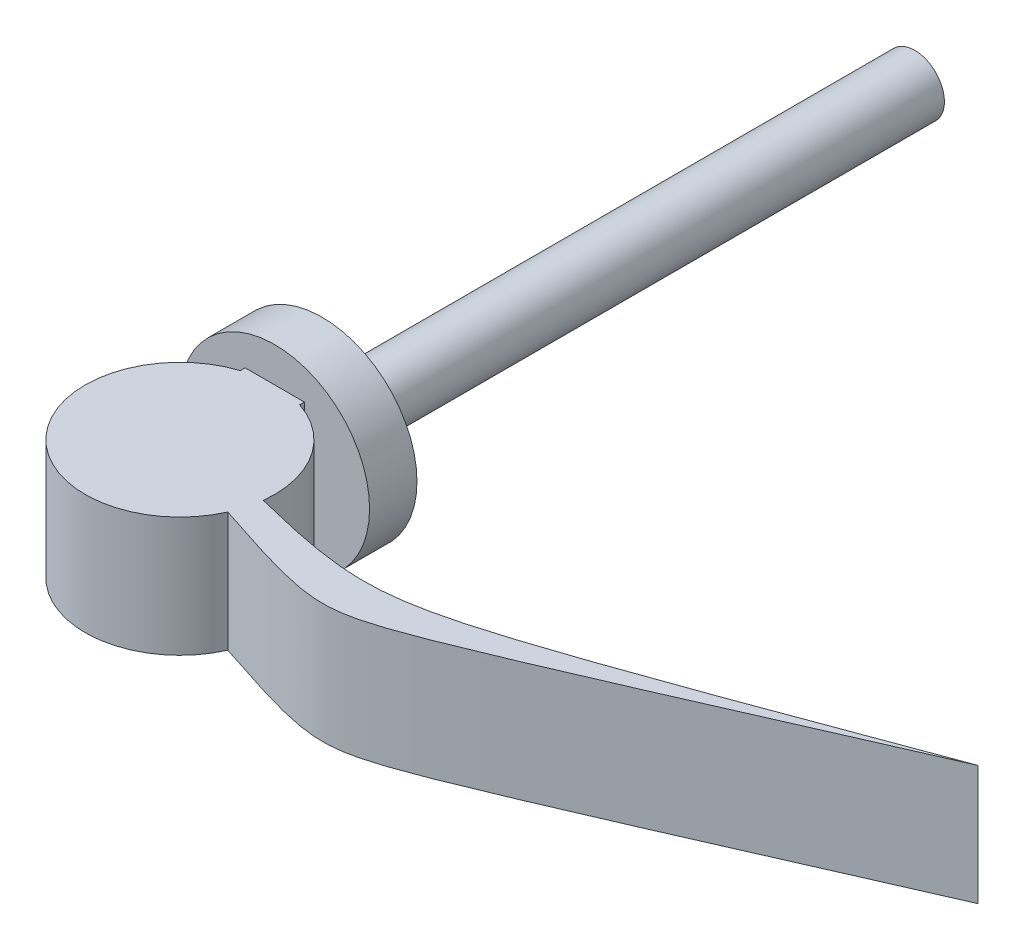
SolidWorks part; units mm, degrees
material "Zero density"
ref_plane "Piano frontale" through (0, 0, 0) normal (0, 0, 1) x (1, 0, 0)
ref_plane "Piano superiore" through (0, 0, 0) normal (0, 1, 0) x (1, 0, 0)
ref_plane "Piano destro" through (0, 0, 0) normal (1, 0, 0) x (0, 0, -1)
sketch "Schizzo1" plane through (0, 0, 0) normal (0, 0, 1) x (1, 0, 0)
  circle A0 centre (0, 0) radius 2.5
  dimension "D1" = 5
extrude "GamboVite" add sketch "Schizzo1" along normal blind 50
sketch "Schizzo2" plane through (0, 0, 50) normal (0, 0, 1) x (1, 0, 0)
  circle A0 centre (0, 0) radius 8
  dimension "D1" = 16
extrude "Piattello" add sketch "Schizzo2" along normal blind 4
sketch "Schizzo3" plane through (0, 0, 0) normal (0, 1, 0) x (1, 0, 0)
  line L0 (-8, -54) -> (8, -54) construction
  line L1 (-2.5, -54) -> (2.5, -54)
  line L2 (-2.5, -54) -> (-2.5, -56)
  line L4 (2.5, -54) -> (2.5, -56)
  line L6 (0, -8.8) -> (0, 8.8) construction
  line L7 (2.5, 0) -> (-2.5, 0) construction
  arc A0 (-2.5, -56) -> (2.5, -56) centre (0, -62) ccw
  point P10 (0, -54)
  dimension "D1" = 13
  dimension "D2" = 2
extrude "AggancioLevetta" add sketch "Schizzo3" along normal blind 5.05 and the other way blind 5.05
sketch "Schizzo4" plane through (0, 5.05, 0) normal (0, 1, 0) x (1, 0, 0)
  line L1 (-8, -54) -> (8, -54) construction
  arc A0 (7.9473, -62.9166) -> (7.3032, -65.2656) centre (0, -62) ccw
  conic Q0 (7.3032, -65.2656) -> (57.4656, -52.1326) control (18.8516, -69.1322) rho 0.846412
  conic Q1 (7.9473, -62.9166) -> (57.4656, -52.1326) control (20.1849, -66.0318) rho 0.759
  dimension "D1" = 16
  dimension "D2" = 49.5183
  dimension "D3" = 8.9166
  dimension "D4" = 11.2656
  dimension "D6" = 10.7841
  dimension "D7" = 12.2376
  dimension "D9" = 3.1152
  dimension "D10" = 13.627
  dimension "D11" = 2.2642
extrude "LevaParteSinistra" add sketch "Schizzo4" against normal up to surface (10.1 mm away) up to face at (0, -5.05, 58.125)
